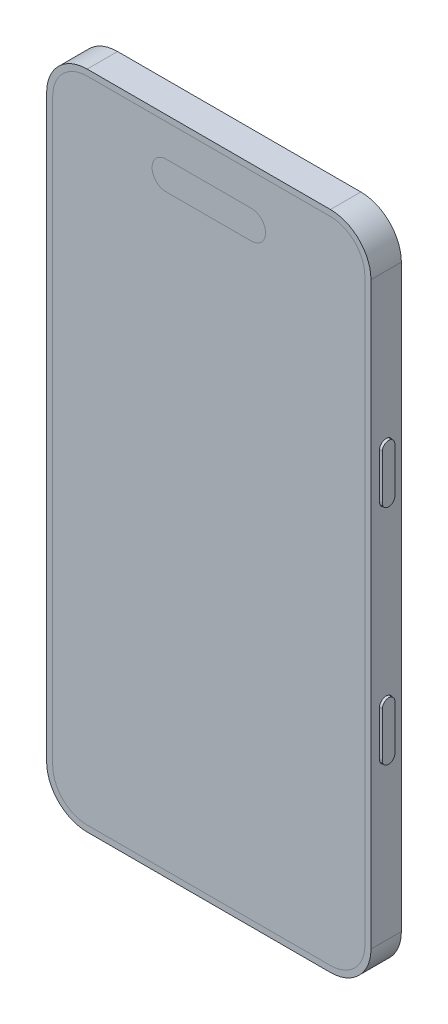
SolidWorks part; units mm, degrees
ref_plane "前视基准面" through (0, 0, 0) normal (0, 0, 1) x (1, 0, 0)
ref_plane "上视基准面" through (0, 0, 0) normal (0, 1, 0) x (1, 0, 0)
ref_plane "右视基准面" through (0, 0, 0) normal (1, 0, 0) x (0, 0, -1)
other "Configuration Table"
sketch "草图1" plane through (0, 0, 0) normal (0, 0, 1) x (1, 0, 0)
  line L1 (-30, -81.5) -> (30, -81.5)
  line L2 (-40, -71.5) -> (-40, 71.5)
  line L3 (-30, 81.5) -> (30, 81.5)
  line L4 (40, -71.5) -> (40, 71.5)
  line L5 (-40, -81.5) -> (40, 81.5) construction
  line L6 (-40, 81.5) -> (40, -81.5) construction
  arc A0 (30, -81.5) -> (40, -71.5) centre (30, -71.5) ccw
  arc A1 (-30, -81.5) -> (-40, -71.5) centre (-30, -71.5) cw
  arc A2 (-40, 71.5) -> (-30, 81.5) centre (-30, 71.5) cw
  arc A3 (40, 71.5) -> (30, 81.5) centre (30, 71.5) ccw
  point P0 (0, 0)
  dimension "D3" = 10
  dimension "D1" = 163
  dimension "D2" = 80
extrude "凸台-拉伸1" add sketch "草图1" along normal blind 7.5
sketch "草图4" plane through (0, 0, 7.5) normal (0, 0, 1) x (1, 0, 0)
  line L0 (-10.5, 68.5) -> (10.5, 68.5) construction
  line L1 (-10.5, 72) -> (10.5, 72)
  line L2 (-10.5, 65) -> (10.5, 65)
  line L3 (30, 81.5) -> (-30, 81.5) construction
  arc A0 (-10.5, 72) -> (-10.5, 65) centre (-10.5, 68.5) ccw
  arc A1 (10.5, 65) -> (10.5, 72) centre (10.5, 68.5) ccw
  point P2 (0, 68.5)
  dimension "D1" = 3.5
  dimension "D2" = 21
  dimension "D3" = 9.5
split line "分割线1"
sketch "草图5" plane through (0, 0, 7.5) normal (0, 0, 1) x (1, 0, 0)
  line L0 (40, -71.5) -> (40, 71.5) construction
  line L1 (-30, -81.5) -> (30, -81.5) construction
  line L2 (-40, 71.5) -> (-40, -71.5) construction
  line L3 (30, 81.5) -> (-30, 81.5) construction
  line L4 (40, -71.5) -> (40, 71.5)
  line L5 (-30, -81.5) -> (30, -81.5)
  line L6 (-40, 71.5) -> (-40, -71.5)
  line L7 (30, 81.5) -> (-30, 81.5)
  line L8 (30, 80) -> (-30, 80)
  line L9 (-38.5, 71.5) -> (-38.5, -71.5)
  line L10 (-30, -80) -> (30, -80)
  line L11 (38.5, -71.5) -> (38.5, 71.5)
  arc A0 (40, 71.5) -> (30, 81.5) centre (30, 71.5) ccw construction
  arc A1 (30, -81.5) -> (40, -71.5) centre (30, -71.5) ccw construction
  arc A2 (-40, -71.5) -> (-30, -81.5) centre (-30, -71.5) ccw construction
  arc A3 (-30, 81.5) -> (-40, 71.5) centre (-30, 71.5) ccw construction
  arc A4 (40, 71.5) -> (30, 81.5) centre (30, 71.5) ccw
  arc A5 (30, -81.5) -> (40, -71.5) centre (30, -71.5) ccw
  arc A6 (-40, -71.5) -> (-30, -81.5) centre (-30, -71.5) ccw
  arc A7 (-30, 81.5) -> (-40, 71.5) centre (-30, 71.5) ccw
  arc A8 (-30, 80) -> (-38.5, 71.5) centre (-30, 71.5) ccw
  arc A9 (-38.5, -71.5) -> (-30, -80) centre (-30, -71.5) ccw
  arc A10 (30, -80) -> (38.5, -71.5) centre (30, -71.5) ccw
  arc A11 (38.5, 71.5) -> (30, 80) centre (30, 71.5) ccw
  dimension "D1" = 1.5
split line "分割线2"
sketch "草图6" plane through (0, 0, 0) normal (0, 0, -1) x (-1, 0, 0)
  line L0 (-40, -71.5) -> (-40, 71.5) construction
  line L1 (-29, 38.5) -> (-7, 38.5)
  line L2 (-37, 46.5) -> (-37, 68.5)
  line L3 (-29, 76.5) -> (-7, 76.5)
  line L4 (1, 46.5) -> (1, 68.5)
  line L5 (-37, 38.5) -> (1, 76.5) construction
  line L6 (-37, 76.5) -> (1, 38.5) construction
  line L7 (-30, 81.5) -> (30, 81.5) construction
  line L8 (-25.7942, 66.5) -> (-25.7942, 48.5)
  line L9 (-25.7942, 48.5) -> (-10.2058, 57.5)
  line L10 (-10.2058, 57.5) -> (-25.7942, 66.5)
  line L11 (1, 57.5) -> (-37, 57.5) construction
  line L12 (-25.7942, 57.5) -> (-10.2058, 57.5)
  circle A0 centre (-25.7942, 66.5) radius 7.5
  circle A1 centre (-10.2058, 57.5) radius 7.5
  circle A2 centre (-25.7942, 48.5) radius 7.5
  arc A3 (-29, 38.5) -> (-37, 46.5) centre (-29, 46.5) cw
  arc A4 (-7, 38.5) -> (1, 46.5) centre (-7, 46.5) ccw
  arc A5 (1, 68.5) -> (-7, 76.5) centre (-7, 68.5) ccw
  arc A6 (-37, 68.5) -> (-29, 76.5) centre (-29, 68.5) cw
  circle A7 centre (-10.2058, 69.5) radius 2
  point P0 (-18, 57.5)
  point P15 (-18, 57.5)
  dimension "D6" = 15
  dimension "D7" = 8
  dimension "D8" = 4
  dimension "D1" = 38
  dimension "D2" = 38
  dimension "D3" = 3
  dimension "D4" = 5
  dimension "D5" = 18
  dimension "D9" = 12
extrude "凸台-拉伸2" add sketch "草图6" along normal blind 1.2 contours L3 A5 L4 A4 L1 A3 L2 A6
extrude "凸台-拉伸3" add sketch "草图6<3>" along normal blind 4 contours A0 | A1 | A2
sketch "草图6<3>" plane through (0, 0, 0) normal (0, 0, -1) x (-1, 0, 0) same geometry as "草图6"
extrude "凸台-拉伸4" add sketch "草图6<4>" along normal blind 2 contours A7
sketch "草图6<4>" plane through (0, 0, 0) normal (0, 0, -1) x (-1, 0, 0) same geometry as "草图6"
sketch "草图10" plane through (0, 0, 0) normal (0, 0, -1) x (-1, 0, 0)
  circle A0 centre (-25.7942, 48.5) radius 7.5 construction
  circle A1 centre (-10.2058, 57.5) radius 7.5 construction
  circle A2 centre (-25.7942, 66.5) radius 7.5 construction
  circle A3 centre (-25.7942, 48.5) radius 7.5
  circle A4 centre (-10.2058, 57.5) radius 7.5
  circle A5 centre (-25.7942, 66.5) radius 7.5
  circle A9 centre (-25.7942, 66.5) radius 6.5
  circle A10 centre (-25.7942, 66.5) radius 6.5
  circle A12 centre (-10.2058, 57.5) radius 6.5
  circle A13 centre (-10.2058, 57.5) radius 6.5
  circle A15 centre (-25.7942, 48.5) radius 6.5
  circle A16 centre (-25.7942, 48.5) radius 6.5
  dimension "D1" = 1
  dimension "D2" = 1
  dimension "D3" = 1
split line "分割线3"
sketch "草图11" plane through (0, 0, -1.2) normal (0, 0, -1) x (-1, 0, 0)
  circle A0 centre (-10.2058, 44.5) radius 1.25
  point P2 (-10.2058, 69.5)
  dimension "D2" = 2.5
  dimension "D1" = 25
split line "分割线4"
sketch "草图14" plane through (-40, 0, 0) normal (-1, 0, 0) x (0, 0, 1)
  line L0 (7.5, 71.5) -> (7.5, -71.5) construction
  line L1 (3.225, 53.36) -> (4.275, 53.36)
  line L2 (2.575, 52.71) -> (2.575, 48.01)
  line L3 (3.225, 47.36) -> (4.275, 47.36)
  line L4 (4.925, 52.71) -> (4.925, 48.01)
  line L5 (2.575, 53.36) -> (4.925, 47.36) construction
  line L6 (2.575, 47.36) -> (4.925, 53.36) construction
  line L7 (7.5, 81.5) -> (0, 81.5) construction
  arc A0 (3.225, 47.36) -> (2.575, 48.01) centre (3.225, 48.01) cw
  arc A1 (4.275, 47.36) -> (4.925, 48.01) centre (4.275, 48.01) ccw
  arc A2 (4.925, 52.71) -> (4.275, 53.36) centre (4.275, 52.71) ccw
  arc A3 (2.575, 52.71) -> (3.225, 53.36) centre (3.225, 52.71) cw
  point P0 (3.75, 50.36)
  dimension "D5" = 0.65
  dimension "D1" = 3.75
  dimension "D2" = 6
  dimension "D3" = 2.35
  dimension "D4" = 31.14
extrude "切除-拉伸2" cut sketch "草图14" against normal mid plane 1.2
sketch "草图15" plane through (-40, 0, 0) normal (-1, 0, 0) x (0, 0, 1)
  line L0 (4.925, 52.71) -> (4.925, 48.01) construction
  line L1 (4.925, 52.71) -> (4.925, 48.01)
  line L2 (4.825, 52.71) -> (4.825, 48.01)
  line L3 (4.275, 52.71) -> (4.275, 48.01) construction
  line L4 (3.725, 52.71) -> (3.725, 48.01)
  arc A0 (4.275, 47.36) -> (4.925, 48.01) centre (4.275, 48.01) ccw construction
  arc A1 (4.925, 52.71) -> (4.275, 53.36) centre (4.275, 52.71) ccw construction
  arc A2 (4.275, 47.36) -> (4.925, 48.01) centre (4.275, 48.01) ccw
  arc A3 (4.925, 52.71) -> (4.275, 53.36) centre (4.275, 52.71) ccw
  arc A4 (4.275, 47.46) -> (4.825, 48.01) centre (4.275, 48.01) ccw
  arc A5 (4.825, 52.71) -> (4.275, 53.26) centre (4.275, 52.71) ccw
  arc A6 (4.275, 47.46) -> (3.725, 48.01) centre (4.275, 48.01) cw
  arc A7 (3.725, 52.71) -> (4.275, 53.26) centre (4.275, 52.71) cw
  dimension "D1" = 0.1
extrude "凸台-拉伸7" add sketch "草图15" along normal mid plane 1.2 contours A7 A5 L2 A4 A6 L4
sketch "草图16" plane through (-40, 0, 0) normal (-1, 0, 0) x (0, 0, 1)
  line L0 (3.75, 71.5) -> (3.75, -71.5) construction
  line L1 (7.5, 71.5) -> (0, 71.5) construction
  line L2 (7.5, -71.5) -> (0, -71.5) construction
  line L3 (3.75, 35.77) -> (3.75, 27.23) construction
  line L4 (5.38, 35.77) -> (5.38, 27.23)
  line L5 (2.12, 35.77) -> (2.12, 27.23)
  line L6 (3.75, 20.77) -> (3.75, 12.23) construction
  line L7 (5.38, 20.77) -> (5.38, 12.23)
  line L8 (2.12, 20.77) -> (2.12, 12.23)
  line L10 (7.5, 81.5) -> (0, 81.5) construction
  arc A0 (5.38, 35.77) -> (2.12, 35.77) centre (3.75, 35.77) ccw
  arc A1 (2.12, 27.23) -> (5.38, 27.23) centre (3.75, 27.23) ccw
  arc A2 (5.38, 20.77) -> (2.12, 20.77) centre (3.75, 20.77) ccw
  arc A3 (2.12, 12.23) -> (5.38, 12.23) centre (3.75, 12.23) ccw
  point P8 (3.75, 31.5)
  point P13 (3.75, 16.5)
  point P20 (3.75, 37.4)
  point P23 (22.9659, 64.8678)
  dimension "D1" = 3.26
  dimension "D2" = 5.9
  dimension "D3" = 50
  dimension "D4" = 65
extrude "切除-拉伸3" cut sketch "草图16" against normal blind 0.6
sketch "草图17" plane through (-40, 0, 0) normal (-1, 0, 0) x (0, 0, 1)
  line L4 (2.22, 35.77) -> (2.22, 27.23)
  line L5 (5.28, 27.23) -> (5.28, 35.77)
  line L6 (2.22, 35.77) -> (2.22, 27.23)
  line L7 (5.28, 27.23) -> (5.28, 35.77)
  line L10 (2.22, 20.77) -> (2.22, 12.23)
  line L11 (5.28, 12.23) -> (5.28, 20.77)
  line L12 (2.22, 20.77) -> (2.22, 12.23)
  line L13 (5.28, 12.23) -> (5.28, 20.77)
  arc A4 (5.28, 35.77) -> (2.22, 35.77) centre (3.75, 35.77) ccw
  arc A5 (2.22, 27.23) -> (5.28, 27.23) centre (3.75, 27.23) ccw
  arc A6 (5.28, 35.77) -> (2.22, 35.77) centre (3.75, 35.77) ccw
  arc A7 (2.22, 27.23) -> (5.28, 27.23) centre (3.75, 27.23) ccw
  arc A10 (5.28, 20.77) -> (2.22, 20.77) centre (3.75, 20.77) ccw
  arc A11 (2.22, 12.23) -> (5.28, 12.23) centre (3.75, 12.23) ccw
  arc A12 (5.28, 20.77) -> (2.22, 20.77) centre (3.75, 20.77) ccw
  arc A13 (2.22, 12.23) -> (5.28, 12.23) centre (3.75, 12.23) ccw
  dimension "D1" = 0.1
  dimension "D2" = 0.1
extrude "凸台-拉伸8" add sketch "草图17" along normal mid plane 1.2
sketch "草图18" plane through (40, 0, 0) normal (1, 0, 0) x (0, 0, -1)
  line L0 (-3.75, 71.5) -> (-3.75, -71.5) construction
  line L1 (-7.5, 71.5) -> (0, 71.5) construction
  line L2 (-7.5, -71.5) -> (0, -71.5) construction
  line L3 (-3.75, 34.05) -> (-3.75, 22.95) construction
  line L4 (-2.1, 34.05) -> (-2.1, 22.95)
  line L5 (-5.4, 34.05) -> (-5.4, 22.95)
  line L6 (-3.75, -20.95) -> (-3.75, -32.05) construction
  line L7 (-2.1, -20.95) -> (-2.1, -32.05)
  line L8 (-5.4, -20.95) -> (-5.4, -32.05)
  line L9 (-7.5, 81.5) -> (0, 81.5) construction
  line L10 (-7.5, -81.5) -> (0, -81.5) construction
  arc A0 (-2.1, 34.05) -> (-5.4, 34.05) centre (-3.75, 34.05) ccw
  arc A1 (-5.4, 22.95) -> (-2.1, 22.95) centre (-3.75, 22.95) ccw
  arc A2 (-2.1, -20.95) -> (-5.4, -20.95) centre (-3.75, -20.95) ccw
  arc A3 (-5.4, -32.05) -> (-2.1, -32.05) centre (-3.75, -32.05) ccw
  point P8 (-3.75, 28.5)
  point P13 (-3.75, -26.5)
  point P20 (-3.75, 35.7)
  dimension "D1" = 7.2
  dimension "D2" = 3.3
  dimension "D3" = 53
  dimension "D4" = 55
extrude "切除-拉伸4" cut sketch "草图18" against normal blind 0.6
sketch "草图19" plane through (40, 0, 0) normal (1, 0, 0) x (0, 0, -1)
  line L8 (-5.3, 34.05) -> (-5.3, 22.95)
  line L9 (-2.2, 22.95) -> (-2.2, 34.05)
  line L10 (-5.3, 34.05) -> (-5.3, 22.95)
  line L11 (-2.2, 22.95) -> (-2.2, 34.05)
  line L14 (-5.3, -20.95) -> (-5.3, -32.05)
  line L15 (-2.2, -32.05) -> (-2.2, -20.95)
  line L16 (-5.3, -20.95) -> (-5.3, -32.05)
  line L17 (-2.2, -32.05) -> (-2.2, -20.95)
  arc A7 (-5.3, 22.95) -> (-2.2, 22.95) centre (-3.75, 22.95) ccw
  arc A8 (-2.2, 34.05) -> (-5.3, 34.05) centre (-3.75, 34.05) ccw
  arc A9 (-5.3, 22.95) -> (-2.2, 22.95) centre (-3.75, 22.95) ccw
  arc A10 (-2.2, 34.05) -> (-5.3, 34.05) centre (-3.75, 34.05) ccw
  arc A13 (-2.2, -20.95) -> (-5.3, -20.95) centre (-3.75, -20.95) ccw
  arc A14 (-5.3, -32.05) -> (-2.2, -32.05) centre (-3.75, -32.05) ccw
  arc A15 (-2.2, -20.95) -> (-5.3, -20.95) centre (-3.75, -20.95) ccw
  arc A16 (-5.3, -32.05) -> (-2.2, -32.05) centre (-3.75, -32.05) ccw
  dimension "D1" = 0.1
  dimension "D2" = 0.1
extrude "凸台-拉伸9" add sketch "草图19" along normal mid plane 1.2
sketch "草图21" plane through (0, -81.5, 0) normal (0, -1, 0) x (1, 0, 0)
  line L0 (-40, 3.75) -> (40, 3.75) construction
  line L1 (-40, 7.5) -> (-40, 0) construction
  line L2 (40, 7.5) -> (40, 0) construction
  line L3 (-4.5, 3.75) -> (4.5, 3.75) construction
  line L4 (-4.5, 5.25) -> (4.5, 5.25)
  line L5 (-4.5, 2.25) -> (4.5, 2.25)
  circle A0 centre (21, 3.75) radius 0.75
  circle A1 centre (18.5, 3.75) radius 0.75
  circle A2 centre (16, 3.75) radius 0.75
  circle A3 centre (13.5, 3.75) radius 0.75
  circle A4 centre (11, 3.75) radius 0.75
  circle A5 centre (-16, 3.75) radius 0.75
  circle A6 centre (-13.5, 3.75) radius 0.75
  circle A7 centre (-11, 3.75) radius 0.75
  arc A8 (-4.5, 5.25) -> (-4.5, 2.25) centre (-4.5, 3.75) ccw
  arc A9 (4.5, 2.25) -> (4.5, 5.25) centre (4.5, 3.75) ccw
  circle A10 centre (-8, 3.75) radius 0.65
  circle A11 centre (8, 3.75) radius 0.65
  point P24 (0, 3.75)
  point P33 (0, 0)
  point P34 (6.5562, 3.75)
  point P35 (-7.2666, 3.75)
  point P36 (0, 0)
  point P37 (0, 0)
  point P38 (-8.5128, 3.75)
  point P39 (8.7963, 3.75)
  point P40 (0, 0)
  point P41 (0, 0)
  point P42 (7.8623, 3.75)
  point P43 (6, 3.75)
  point P44 (-6, 3.75)
  dimension "D1" = 1.5
  dimension "D10" = 1.5
  dimension "D8" = 1.3
  dimension "D2" = 19
  dimension "D4" = 2.5
  dimension "D5" = 24
  dimension "D7" = 2.5
  dimension "D9" = 2
  dimension "D11" = 2
  dimension "D12" = 32
  dimension "D3" = 5
  dimension "D6" = 3
extrude "切除-拉伸5" cut sketch "草图21" against normal blind 3.2
